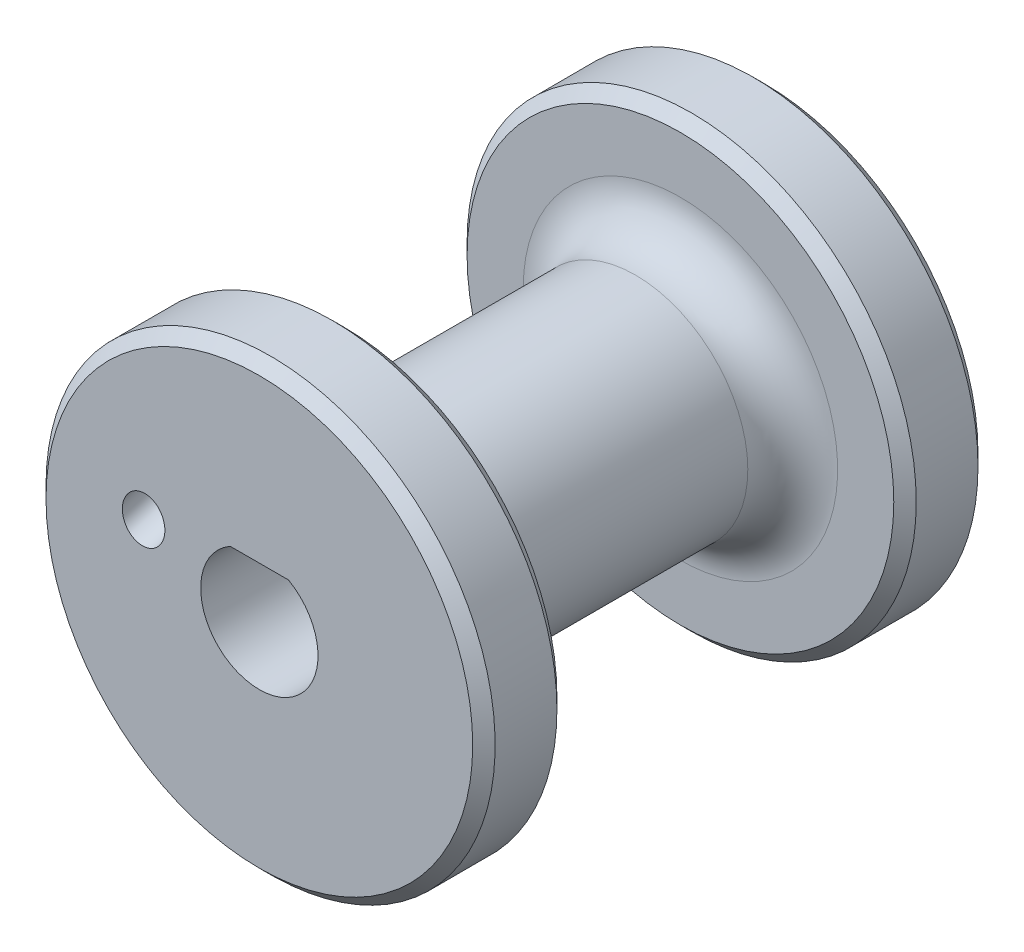
SolidWorks part; units mm, degrees
ref_plane "Front Plane" through (0, 0, 0) normal (0, 0, 1) x (1, 0, 0)
ref_plane "Top Plane" through (0, 0, 0) normal (0, 1, 0) x (1, 0, 0)
ref_plane "Right Plane" through (0, 0, 0) normal (1, 0, 0) x (0, 0, -1)
sketch "Sketch1" plane through (0, 0, 0) normal (0, 0, 1) x (1, 0, 0)
  circle A0 centre (0, 0) radius 3.3175
  circle A1 centre (0, 0) radius 6.35
  dimension "D1" = 6.635
  dimension "D2" = 12.7
extrude "Boss-Extrude1" add sketch "Sketch1" along normal blind 9.525 and the other way blind 9.525 contours A1 A0 region at (-6.1704, 0, 0)
sketch "Sketch2" plane through (0, 0, -9.525) normal (0, 0, -1) x (-1, 0, 0)
  circle A0 centre (0, 0) radius 12.7
  circle A1 centre (0, 0) radius 6.35 construction
  circle A2 centre (0, 0) radius 6.35 construction
  circle A3 centre (0, 0) radius 3.3175 construction
  circle A4 centre (0, 0) radius 3.3175
  circle M3 centre (0, 0) radius 3.3175
  circle M4 centre (0, 0) radius 6.35
  dimension "D1" = 6.35
extrude "Boss-Extrude3" add sketch "Sketch2" along normal blind 4.7625 contours M4 M3 | A0 M4 region at (12.3408, 0, -9.525) region at (6.1704, 0, -9.525)
mirror "Mirror1" about plane through (0, 0, 0) normal (0, 0, 1) of "Boss-Extrude3"
sketch "Sketch3" plane through (0, 0, -14.2875) normal (0, 0, -1) x (-1, 0, 0)
  circle A0 centre (0, 0) radius 3.3175 construction
  circle A1 centre (0, 0) radius 3.3175
extrude "Boss-Extrude4" add sketch "Sketch3" against normal through all
fillet "Fillet1" radius 2.54 2 edges at (6.35, 0, 9.525) (6.35, 0, -9.525)
chamfer "Chamfer1" distance 0.635 angle 45 4 edges at (-12.7, 0, -14.2875) (-12.7, 0, -9.525) (-12.7, 0, 9.525) (-12.7, 0, 14.2875)
sketch "Sketch4" plane through (0, 0, 14.2875) normal (0, 0, 1) x (1, 0, 0)
  line L0 (-1.651, 2.8775) -> (1.651, 2.8775)
  circle A3 centre (0, 0) radius 6.35
  circle A4 centre (0, 0) radius 6.35
  circle A5 centre (0, 0) radius 3.3175
  circle A6 centre (0, 0) radius 3.3175
  dimension "D1" = 0
  dimension "D3" = 3.302
  dimension "D2" = 0
extrude "Cut-Extrude1" cut sketch "Sketch4" against normal blind 13.97 contours L0 A6 region at (0, -0.0893, 14.2875)
sketch "Sketch5" plane through (0, 0, 14.2875) normal (0, 0, 1) x (1, 0, 0)
  point P0 (-6.5447, 1.737)
  point P1 (-6.5447, 1.737)
  point P2 (-6.4567, 1.7781)
  point P3 (-6.5447, 1.737)
sketch3d "3DSketch1"
  point P0 (-5.8259, 4.2649, 8.8989)
ref_axis "Axis1" through (-5.8259, 4.2649, 8.8989) along (-0.1199, -0.4216, 0.8988)
ref_plane "Plane1" through (-6.5447, 1.737, 14.2875) normal (-0.1199, -0.4216, 0.8988) x (0.9928, -0.0509, 0.1085)
sketch "Sketch6" plane through (-6.5447, 1.737, 14.2875) normal (-0.1199, -0.4216, 0.8988) x (0.9928, -0.0509, 0.1085)
  circle A0 centre (0, 0) radius 1.1906
  dimension "D1" = 2.3812
extrude "Cut-Extrude2" cut sketch "Sketch6" against normal up to next and the other way up to next
